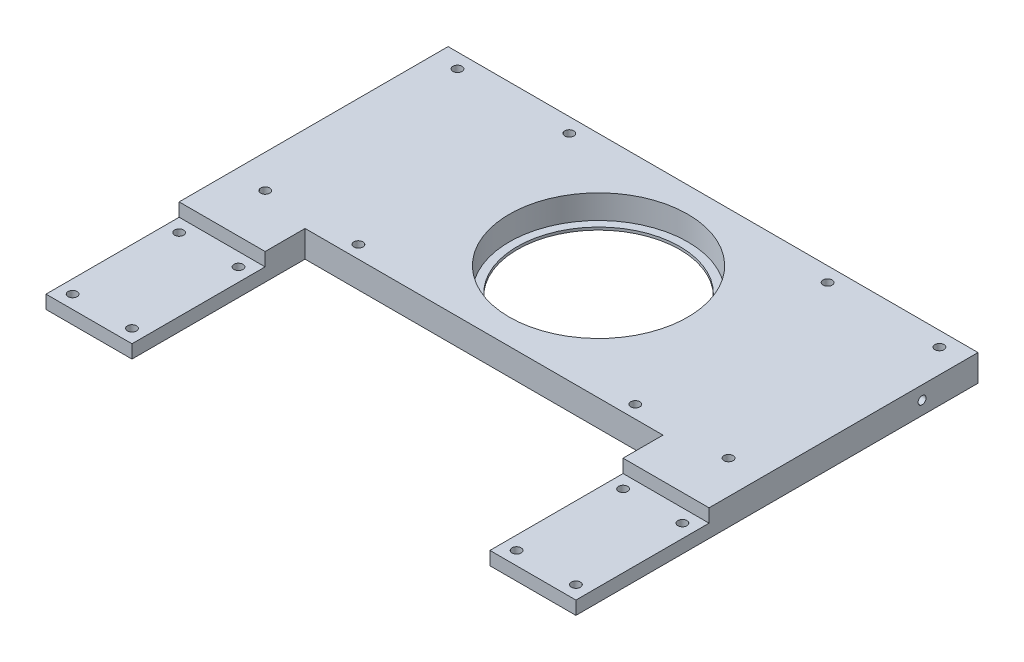
SolidWorks part; units mm, degrees
ref_plane "Ebene vorne" through (0, 0, 0) normal (0, 0, 1) x (1, 0, 0)
ref_plane "Ebene oben" through (0, 0, 0) normal (0, 1, 0) x (1, 0, 0)
ref_plane "Ebene rechts" through (0, 0, 0) normal (1, 0, 0) x (0, 0, -1)
sketch "Skizze1" plane through (0, 0, 0) normal (0, 1, 0) x (1, 0, 0)
  line L1 (-99.5, -200) -> (99.5, -200)
  line L2 (-99.5, -200) -> (-99.5, 200)
  line L3 (-99.5, 200) -> (99.5, 200)
  line L4 (99.5, -200) -> (99.5, 200)
  line L5 (-99.5, -200) -> (99.5, 200) construction
  line L6 (-99.5, 200) -> (99.5, -200) construction
  point P0 (0, 0)
  dimension "D1" = 199
  dimension "D2" = 400
extrude "Aufsatz-Linear austragen1" add sketch "Skizze1" along normal blind 10
ref_plane "Ebene1" through (0, -92.6125, 77.7111) normal (0, -0.766, 0.6428) x (1, 0, 0)
sketch "Skizze2" plane through (0, -92.6125, 77.7111) normal (0, -0.766, 0.6428) x (1, 0, 0)
  line L1 (-99.5, 159.6368) -> (99.5, 159.6368) construction
  circle A0 centre (0, 139.6368) radius 5
  dimension "D1" = 10
  dimension "D2" = 20
extrude "Schnitt-Linear austragen1" [suppressed] cut sketch "Skizze2" against normal blind 30 and the other way blind 10
sketch "Skizze3" [suppressed] plane through (0, -67.9923, 57.0523) normal (0, -0.766, 0.6428) x (1, 0, 0)
  circle A0 centre (0, 101.3345) radius 5
  dimension "D1" = 10
extrude "Aufsatz-Linear austragen2" [suppressed] add sketch "Skizze3" along normal blind 0.1
sketch "Skizze4" plane through (0, -92.6125, 77.7111) normal (0, -0.766, 0.6428) x (1, 0, 0)
  line L0 (0, 159.6368) -> (0, 159.9002) construction
  line L1 (-99.5, 159.6368) -> (99.5, 159.6368) construction
  line L2 (-25, 159.6368) -> (-25, 194.6368)
  line L3 (-25, 194.6368) -> (25, 194.6368)
  line L4 (-25, 159.6368) -> (25, 159.6368)
  line L5 (25, 159.6368) -> (25, 194.6368)
  point P10 (0, 194.6368)
  dimension "D1" = 50
  dimension "D2" = 35
extrude "Aufsatz-Linear austragen3" [suppressed] add sketch "Skizze4" against normal blind 10 separate body
sketch "Skizze5" plane through (0, 10, 0) normal (0, 1, 0) x (1, 0, 0)
  line L0 (0, 0) -> (0, -200) construction
  line L1 (-99.5, -200) -> (99.5, -200) construction
  line L2 (99.5, -200) -> (18, -200)
  line L3 (-18, -200) -> (-99.5, -46)
  line L4 (-99.5, 200) -> (-99.5, -200) construction
  line L5 (-99.5, -46) -> (-99.5, -200)
  line L6 (-99.5, -200) -> (-18, -200)
  line L7 (99.5, -46) -> (99.5, -200)
  line L8 (18, -200) -> (99.5, -46)
  line L9 (-99.5, 200) -> (-99.5, 105)
  line L10 (-99.5, 105) -> (99.5, 105)
  line L11 (99.5, -200) -> (99.5, 200) construction
  line L12 (99.5, 105) -> (99.5, 200)
  line L13 (99.5, 200) -> (-99.5, 200)
  line L14 (67.211, -46) -> (-67.211, -46)
  line L15 (-67.211, -46) -> (-2.6461, -168)
  line L16 (67.211, -46) -> (2.6461, -168)
  line L17 (-2.6461, -168) -> (2.6461, -168)
  line L18 (2.6461, -168) -> (0, -173) construction
  line L19 (-2.6461, -168) -> (0, -173) construction
  point P27 (0, -46)
  dimension "D1" = 36
  dimension "D2" = 154
  dimension "D3" = 95
  dimension "D4" = 32
  dimension "D5" = 27
extrude "Schnitt-Linear austragen2" cut sketch "Skizze5" against normal blind 10
sketch "Skizze6" plane through (0, 10, 0) normal (0, 1, 0) x (1, 0, 0)
  line L0 (0, -200) -> (0, -168) construction
  line L1 (-18, -200) -> (18, -200) construction
  line L2 (-2.6461, -168) -> (2.6461, -168) construction
  line L3 (0, -186.59) -> (-21.075, -186.59) construction
  circle A0 centre (-11, -195) radius 1.7
  circle A1 centre (-11, -178.18) radius 1.7
  circle A2 centre (11, -195) radius 1.7
  circle A3 centre (11, -178.18) radius 1.7
  dimension "D1" = 3.4
  dimension "D2" = 11
  dimension "D3" = 5
  dimension "D4" = 13.41
extrude "Schnitt-Linear austragen3" cut sketch "Skizze6" against normal through all
sketch "Skizze7" plane through (0, 0, 0) normal (0, -1, 0) x (1, 0, 0)
  line L0 (-11, 195) -> (-11, 200) construction
  line L1 (-18, 200) -> (18, 200) construction
  line L2 (-11, 195) -> (-5.1092, 195) construction
  line L3 (-11, 198.4064) -> (-8.05, 196.7032)
  line L4 (-8.05, 196.7032) -> (-8.05, 193.2968)
  line L5 (-11, 191.5936) -> (-8.05, 193.2968)
  line L6 (-11, 191.5936) -> (-13.95, 193.2968)
  line L7 (-13.95, 196.7032) -> (-13.95, 193.2968)
  line L8 (-11, 198.4064) -> (-13.95, 196.7032)
  line L9 (0, 200) -> (0, 121.6034) construction
  line L10 (11, 195) -> (11, 178.18) construction
  line L11 (11, 186.59) -> (0, 186.59) construction
  line L12 (11, 198.4064) -> (8.05, 196.7032)
  line L13 (11, 191.5936) -> (8.05, 193.2968)
  line L14 (8.05, 196.7032) -> (8.05, 193.2968)
  line L15 (11, 191.5936) -> (13.95, 193.2968)
  line L16 (13.95, 196.7032) -> (13.95, 193.2968)
  line L17 (11, 198.4064) -> (13.95, 196.7032)
  line L18 (-8.05, 176.4768) -> (-8.05, 179.8832)
  line L19 (-11, 181.5864) -> (-13.95, 179.8832)
  line L20 (-11, 181.5864) -> (-8.05, 179.8832)
  line L21 (-13.95, 176.4768) -> (-13.95, 179.8832)
  line L22 (-11, 174.7736) -> (-13.95, 176.4768)
  line L23 (-11, 174.7736) -> (-8.05, 176.4768)
  line L24 (8.05, 176.4768) -> (8.05, 179.8832)
  line L25 (11, 181.5864) -> (8.05, 179.8832)
  line L26 (11, 181.5864) -> (13.95, 179.8832)
  line L27 (13.95, 176.4768) -> (13.95, 179.8832)
  line L28 (11, 174.7736) -> (13.95, 176.4768)
  line L29 (11, 174.7736) -> (8.05, 176.4768)
  point P10 (-8.05, 195)
  dimension "D1" = 120
  dimension "D2" = 5.9
extrude "Schnitt-Linear austragen4" cut sketch "Skizze7" against normal blind 4
sketch "Skizze8" plane through (0, 10, 0) normal (0, 1, 0) x (1, 0, 0)
  line L0 (99.5, 95.41) -> (78.872, 95.41) construction
  line L1 (99.5, -46) -> (99.5, 105) construction
  line L2 (-99.5, 105) -> (99.5, 105) construction
  dimension "D1" = 9.59
ref_plane "Ebene2" through (0, 52.8485, -44.3452) normal (0, 0.766, -0.6428) x (-1, 0, 0)
sketch "Skizze9" plane through (0, 52.8485, -44.3452) normal (0, 0.766, -0.6428) x (-1, 0, 0)
  line L0 (-99.5, -66.6604) -> (-78.872, -66.6604) construction
  line L1 (-99.5, 41.6659) -> (-99.5, -74.0068) construction
  line L2 (0, -45.2589) -> (0, -16.2619) construction
  circle A0 centre (-94.5, -66.6604) radius 1.7
  circle A1 centre (94.5, -66.6604) radius 1.7
  circle A2 centre (-30, -66.6604) radius 1.7
  circle A3 centre (30, -66.6604) radius 1.7
  dimension "D1" = 3.4
  dimension "D2" = 5
  dimension "D3" = 30
extrude "Schnitt-Linear austragen5" [suppressed] cut sketch "Skizze9" against normal through all and the other way through all
ref_plane "Ebene3" through (0, 45.1881, -37.9173) normal (0, 0.766, -0.6428) x (-1, 0, 0)
sketch "Skizze10" [suppressed] plane through (0, 55.0361, -46.1808) normal (0, 0.766, -0.6428) x (-1, 0, 0)
  line L0 (-95, -81.9813) -> (-100, -81.9813) construction
  line L1 (-95, -81.9813) -> (-95, -30.0694) construction
  line L2 (-95, -78.7482) -> (-97.8, -80.3647)
  line L3 (-97.8, -80.3647) -> (-97.8, -83.5979)
  line L4 (-95, -85.2145) -> (-97.8, -83.5979)
  line L5 (-95, -85.2145) -> (-92.2, -83.5979)
  line L6 (-92.2, -80.3647) -> (-92.2, -83.5979)
  line L7 (-95, -78.7482) -> (-92.2, -80.3647)
  line L8 (0, 0) -> (0, -45.6283) construction
  line L9 (-30, -81.9813) -> (-95, -81.9813) construction
  line L10 (-62.5, -81.9813) -> (-62.5, -23.1343) construction
  line L11 (-32.8, -80.3647) -> (-32.8, -83.5979)
  line L12 (-30, -85.2145) -> (-32.8, -83.5979)
  line L13 (-30, -85.2145) -> (-27.2, -83.5979)
  line L14 (-27.2, -80.3647) -> (-27.2, -83.5979)
  line L15 (-30, -78.7482) -> (-27.2, -80.3647)
  line L16 (-30, -78.7482) -> (-32.8, -80.3647)
  line L17 (95, -78.7482) -> (92.2, -80.3647)
  line L18 (92.2, -80.3647) -> (92.2, -83.5979)
  line L19 (95, -85.2145) -> (92.2, -83.5979)
  line L20 (95, -85.2145) -> (97.8, -83.5979)
  line L21 (97.8, -80.3647) -> (97.8, -83.5979)
  line L22 (95, -78.7482) -> (97.8, -80.3647)
  line L23 (30, -78.7482) -> (32.8, -80.3647)
  line L24 (30, -78.7482) -> (27.2, -80.3647)
  line L25 (27.2, -80.3647) -> (27.2, -83.5979)
  line L26 (30, -85.2145) -> (27.2, -83.5979)
  line L27 (30, -85.2145) -> (32.8, -83.5979)
  line L28 (32.8, -80.3647) -> (32.8, -83.5979)
  point P9 (-97.8, -81.9813)
  point P31 (97.8, -81.9813)
  dimension "D1" = 120
  dimension "D2" = 5.6
extrude "Schnitt-Linear austragen6" [suppressed] cut sketch "Skizze10" against normal blind 10 and the other way blind 5
sketch "Skizze13" plane through (0, 10, 0) normal (0, 1, 0) x (1, 0, 0)
  line L0 (67.211, -46) -> (99.5, -46) construction
  line L1 (67.211, -46) -> (92.4353, -59.3492) construction
  line L2 (99.5, -46) -> (18, -200) construction
  line L3 (0, 0) -> (0, -38.1435) construction
  line L4 (2.6461, -168) -> (67.211, -46) construction
  line L5 (79.8232, -52.6746) -> (99.764, -14.995) construction
  line L6 (99.5, -46) -> (99.5, 105) construction
  line L7 (83.3555, -46) -> (83.3555, -1) construction
  line L8 (93.5, -48.8065) -> (96.9981, -42.1965) construction
  line L9 (83.1285, -76.935) -> (57.9043, -63.5858) construction
  line L10 (71.7911, -70.935) -> (86.3039, -70.935) construction
  circle A0 centre (93.5, -48.8065) radius 1.7
  circle A1 centre (72.5142, -48.8065) radius 1.7
  circle A2 centre (81.7891, -70.935) radius 1.7
  circle A3 centre (-81.7891, -70.935) radius 1.7
  circle A4 centre (-93.5, -48.8065) radius 1.7
  circle A5 centre (-72.5142, -48.8065) radius 1.7
  dimension "D1" = 6
  dimension "D5" = 35
  dimension "D3" = 3.4
  dimension "D6" = 3.4
  dimension "D2" = 6
  dimension "D4" = 6
extrude "Schnitt-Linear austragen7" [suppressed] cut sketch "Skizze13" against normal through all
sketch "Skizze14" plane through (96.7476, 0, 51.2008) normal (0.8839, 0, 0.4678) x (0.4678, 0, -0.8839)
  line L0 (-29.1157, 5) -> (-29.1157, 10)
  line L5 (5.8843, 0) -> (5.8843, 10) construction
  line L6 (-29.1157, 5) -> (5.8843, 5)
  line L7 (5.8843, 10) -> (-168.3519, 10) construction
  line L8 (-29.1157, 10) -> (5.8843, 10)
  line L9 (5.8843, 10) -> (5.8843, 5)
  dimension "D1" = 35
extrude "Schnitt-Linear austragen8" [suppressed] cut sketch "Skizze14" against normal up to surface (28.9525 mm away)
mirror "Spiegeln1" [suppressed] about plane through (0, 0, 0) normal (1, 0, 0)
sketch "Skizze15" [suppressed] plane through (95, 0, 0) normal (1, 0, 0) x (0, 0, -1)
  line L0 (4, 10) -> (4, 0)
  line L1 (4, 0) -> (65, 0)
  line L2 (65, 0) -> (65, 10)
  line L3 (65, 10) -> (4, 10)
extrude "Schnitt-Linear austragen9" [suppressed] cut sketch "Skizze15" against normal through all
sketch "Skizze16" plane through (0, 0, 0) normal (0, -1, 0) x (1, 0, 0)
  line L0 (0, 200) -> (0, 168) construction
  line L1 (-18, 200) -> (18, 200) construction
  line L2 (-2.6461, 168) -> (2.6461, 168) construction
  line L3 (11, 186.59) -> (0, 186.59) construction
  line L4 (11, 195) -> (11, 178.18) construction
  line L6 (-17.5, 183.09) -> (17.5, 183.09)
  line L7 (-17.5, 183.09) -> (-17.5, 190.09)
  line L8 (-17.5, 190.09) -> (17.5, 190.09)
  line L9 (17.5, 183.09) -> (17.5, 190.09)
  line L10 (-17.5, 183.09) -> (17.5, 190.09) construction
  line L11 (-17.5, 190.09) -> (17.5, 183.09) construction
  dimension "D1" = 7
  dimension "D2" = 35
extrude "Schnitt-Linear austragen10" cut sketch "Skizze16" against normal blind 5
sketch "Skizze17" plane through (17.5, 0, 0) normal (-1, 0, 0) x (0, 0, 1)
  line L0 (186.59, 0) -> (186.59, 11.1261) construction
  line L1 (183.09, 0) -> (190.09, 0) construction
  line L2 (183.09, 5) -> (186.59, 8.5)
  line L3 (186.59, 8.5) -> (190.09, 5)
  line L4 (190.09, 5) -> (183.09, 5)
  dimension "D1" = 90
extrude "Schnitt-Linear austragen11" cut sketch "Skizze17" along normal up to surface (35 mm away) up to face at (-17.5, 2.5, 186.59)
sketch "Skizze18" [suppressed] plane through (0, 10, 0) normal (0, 1, 0) x (1, 0, 0)
  line L0 (0, -210) -> (0, 0) construction
  line L1 (-18, -210) -> (18, -210) construction
  line L2 (62.5765, -72.2325) -> (35.4483, -67.5372)
  line L3 (15.3378, -155.8503) -> (-22.1774, -134.6566)
  line L4 (2.8247, -178) -> (62.5765, -72.2325) construction
  line L5 (-15.3378, -155.8503) -> (22.1774, -134.6566)
  line L6 (58.6594, -79.166) -> (40.7308, -76.063)
  line L7 (0, -147.1854) -> (19.5429, -147.1854) construction
  line L8 (0, -95.4) -> (31.4297, -95.4) construction
  line L9 (11.6488, -162.3803) -> (0, -155.7995)
  line L10 (-71.7468, -56) -> (-2.8247, -178) construction
  line L11 (0, -95.4) -> (-37.5153, -116.5937) construction
  line L12 (-37.5153, -116.5937) -> (-39.2566, -117.5774) construction
  line L13 (-11.6488, -162.3803) -> (0, -155.7995)
  line L14 (-58.6594, -79.166) -> (-40.7308, -76.063)
  line L15 (-62.5765, -72.2325) -> (-35.4483, -67.5372)
  circle A0 centre (0, -95.4) radius 33.5
  arc A1 (7.4594, -151.3994) -> (7.4594, -142.9713) centre (9.84, -147.1854) cw
  arc A2 (-7.4594, -151.3994) -> (-7.4594, -142.9713) centre (-9.84, -147.1854) ccw
  circle A3 centre (0, -95.4) radius 45.0879
  point P17 (0, -147.1854)
  point P36 (5, -147.1854)
  point P40 (-5, -147.1854)
  line M16 (62.5765, -72.2325) -> (2.8247, -178)
  line M18 (-2.8247, -178) -> (-71.7468, -56)
  dimension "D2" = 67
  dimension "D5" = 2
  dimension "D4" = 10
  dimension "D1" = 114.6
  dimension "D3" = 7.5
  dimension "D6" = 7.5
extrude "Aufsatz-Linear austragen4" [suppressed] add sketch "Skizze18" against normal blind 10 contours A3 L15 L14 M18 | A3 A0 M16 M18 | A3 L6 L2 M16 | A2 L5 L3 | A3 L3 L5 | L3 A1 L5 | L13 L9 L3 L5 M18 M16
sketch "Skizze19" [suppressed] plane through (0, 0, 0) normal (0, -1, 0) x (1, 0, 0)
  circle A0 centre (0, 35.4) radius 31.5
  circle A1 centre (0, 35.4) radius 33.5
  circle A2 centre (0, 35.4) radius 33.5 construction
  dimension "D1" = 63
extrude "Aufsatz-Linear austragen5" [suppressed] add sketch "Skizze19" against normal blind 1
sketch "Skizze20" plane through (0, 10, 0) normal (0, 1, 0) x (1, 0, 0)
  line L0 (99.5, 99.52) -> (55.4083, 99.52) construction
  line L1 (99.5, -46) -> (99.5, 105) construction
  line L2 (-99.5, 105) -> (99.5, 105) construction
  line L3 (0, 105) -> (0, 96.9732) construction
  line L4 (105, 23.82) -> (35.5869, 23.82) construction
  circle A0 centre (90.5, 99.52) radius 1.7
  circle A1 centre (48.5, 99.52) radius 1.7
  circle A2 centre (-48.5, 99.52) radius 1.7
  circle A3 centre (-90.5, 99.52) radius 1.7
  circle A4 centre (87, 23.82) radius 1.7
  circle A5 centre (52, 23.82) radius 1.7
  circle A6 centre (-87, 23.82) radius 1.7
  circle A7 centre (-52, 23.82) radius 1.7
  dimension "D1" = 3.4
  dimension "D2" = 5.48
  dimension "D3" = 9
  dimension "D4" = 42
  dimension "D5" = 75.7
  dimension "D6" = 12.5
  dimension "D7" = 35
extrude "Schnitt-Linear austragen12" cut sketch "Skizze20" against normal through all
sketch "Skizze21" plane through (0, 10, 0) normal (0, 1, 0) x (1, 0, 0)
  line L0 (-67.211, -46) -> (-67.211, 19)
  line L1 (-67.211, 19) -> (67.211, 19)
  line L2 (67.211, 19) -> (67.211, -46)
  line L3 (67.211, -46) -> (-67.211, -46) construction
  line L4 (-67.211, -46) -> (67.211, -46)
  dimension "D1" = 65
extrude "Schnitt-Linear austragen13" cut sketch "Skizze21" against normal through all
sketch "Skizze22" plane through (0, 10, 0) normal (0, 1, 0) x (1, 0, 0)
  line L0 (-67.211, -46) -> (-2.6461, -168)
  arc A0 (-67.211, -46) -> (-2.6461, -168) centre (60.0769, -56.7211) ccw
  line M19 (-2.6461, -168) -> (-67.211, -46)
extrude "Schnitt-Linear austragen14" cut sketch "Skizze22" against normal through all contours M19 region at (-42.1385, 10, 110.8156)
sketch "Skizze23" plane through (0, 10, 0) normal (0, 1, 0) x (1, 0, 0)
  line L0 (-18, -200) -> (-99.5, -46) construction
  line L1 (-99.5, -46) -> (-18, -200)
  arc A0 (-18, -200) -> (-99.5, -46) centre (114.4449, -31.3416) cw
  arc A2 (-67.211, -46) -> (-2.6461, -168) centre (60.0769, -56.7211) ccw construction
  dimension "D1" = 60
extrude "Aufsatz-Linear austragen6" add sketch "Skizze23" against normal blind 10
mirror "Spiegeln2" about plane through (0, 0, 0) normal (1, 0, 0) of "Aufsatz-Linear austragen6", "Schnitt-Linear austragen14"
sketch "Skizze25" plane through (0, 10, 0) normal (0, 1, 0) x (1, 0, 0)
  line L0 (-99.5, -46) -> (-67.211, -46) construction
  line L1 (-99.5, 4) -> (-99.5, -46) construction
  line L2 (-99.5, 4) -> (-67.211, 4) construction
  line L3 (-67.211, 19) -> (-67.211, -46) construction
  line L4 (-83.3555, 4) -> (-83.3555, -46) construction
  line L5 (-99.5, -21) -> (-67.211, -21) construction
  line L6 (-99.5, 105) -> (-99.5, -46) construction
  circle A0 centre (-94.5, -1) radius 1.7
  circle A1 centre (-72.211, -1) radius 1.7
  circle A2 centre (-72.211, -41) radius 1.7
  circle A3 centre (-94.5, -41) radius 1.7
  dimension "D2" = 3.4
  dimension "D1" = 50
  dimension "D3" = 5
  dimension "D4" = 5
extrude "Schnitt-Linear austragen15" cut sketch "Skizze25" against normal through all
sketch "Skizze26" plane through (-99.5, 0, 0) normal (-1, 0, 0) x (0, 0, 1)
  line L0 (-4, 5) -> (-4, 13.1015)
  line L1 (46, 0) -> (46, 10) construction
  line L2 (46, 5) -> (-4, 5)
  line L4 (-105, 0) -> (46, 0) construction
  line L5 (46, 5) -> (46, 0)
  line L6 (-4, 13.1015) -> (200.6846, 82.5463)
  line L7 (200.6846, 82.5463) -> (242.9972, -41.0376)
  line L8 (242.9972, -41.0376) -> (91.2415, -60.2848)
  line L9 (91.2415, -60.2848) -> (46, 0)
  dimension "D1" = 50
mirror "Spiegeln3" about plane through (0, 0, 0) normal (1, 0, 0) of "Schnitt-Linear austragen15"
extrude "Schnitt-Linear austragen16" cut sketch "Skizze26" against normal through all
sketch "Skizze27" plane through (0, 10, 0) normal (0, 1, 0) x (1, 0, 0)
  line L0 (0, 19) -> (0, 105) construction
  line L1 (67.211, 19) -> (-67.211, 19) construction
  line L2 (-99.5, 105) -> (99.5, 105) construction
  circle A0 centre (0, 62) radius 33.5
  dimension "D1" = 67
extrude "Schnitt-Linear austragen17" cut sketch "Skizze27" against normal through all
sketch "Skizze28" plane through (0, 0, 0) normal (0, -1, 0) x (1, 0, 0)
  circle A0 centre (0, -62) radius 30.5
  circle A1 centre (0, -62) radius 33.5 construction
  circle A2 centre (0, -62) radius 36.0063
  dimension "D1" = 3
extrude "Aufsatz-Linear austragen7" add sketch "Skizze28" against normal blind 1
sketch "Skizze29" plane through (-99.5, 0, 0) normal (-1, 0, 0) x (0, 0, 1)
  line L0 (-105, 5) -> (-93.4233, 5) construction
  line L1 (-105, 0) -> (-105, 10) construction
  circle A0 centre (-84, 5) radius 1.5
  dimension "D1" = 3
  dimension "D2" = 21
extrude "Schnitt-Linear austragen18" cut sketch "Skizze29" against normal blind 10
sketch "Skizze30" plane through (0, 0, -105) normal (0, 0, -1) x (-1, 0, 0)
  line L0 (99.5, 5) -> (60.2539, 5) construction
  line L1 (99.5, 0) -> (99.5, 10) construction
  circle A0 centre (94.5, 5) radius 1.5
  circle A1 centre (78.5, 5) radius 1.5
  dimension "D1" = 3
  dimension "D2" = 5
  dimension "D3" = 21
extrude "Schnitt-Linear austragen19" cut sketch "Skizze30" against normal blind 10
mirror "Spiegeln4" about plane through (0, 0, 0) normal (1, 0, 0) of "Schnitt-Linear austragen18", "Schnitt-Linear austragen19"
sketch "Skizze31" plane through (0, 0, 0) normal (0, -1, 0) x (1, 0, 0)
  line L0 (0, -105) -> (0, -73.0202) construction
  line L1 (-99.5, -105) -> (99.5, -105) construction
  circle A0 centre (-90.5, -99.52) radius 2.95
  circle A1 centre (-48.5, -99.52) radius 2.95
  circle A2 centre (-87, -23.82) radius 2.95
  circle A3 centre (-52, -23.82) radius 2.95
  circle A4 centre (52, -23.82) radius 2.95
  circle A5 centre (87, -23.82) radius 2.95
  circle A6 centre (48.5, -99.52) radius 2.95
  circle A7 centre (90.5, -99.52) radius 2.95
  dimension "D1" = 5.9
extrude "Schnitt-Linear austragen20" cut sketch "Skizze31" against normal blind 3.5
